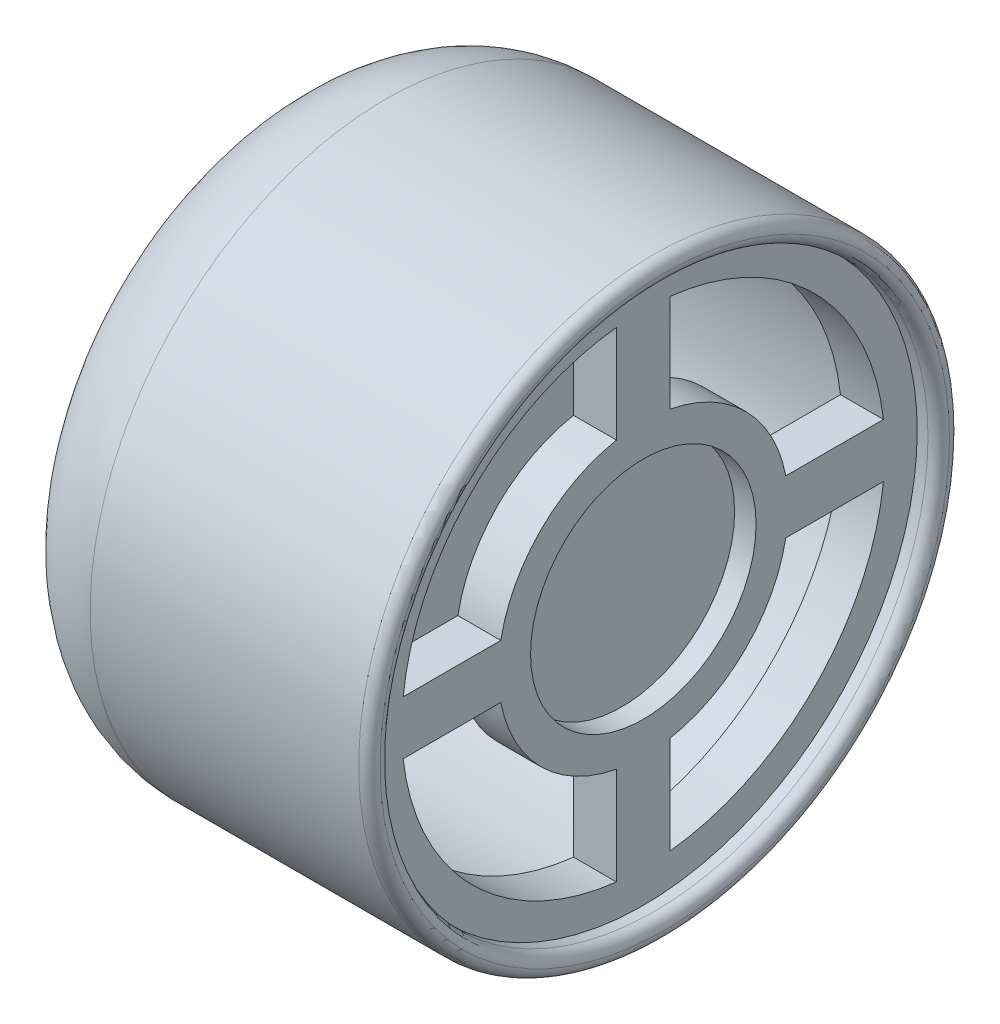
SolidWorks part; units mm, degrees
material "PLA"
ref_plane "Front Plane" through (0, 0, 0) normal (1, 0, 0) x (0, 1, 0)
ref_plane "Top Plane" through (0, 0, 0) normal (0, 0, 1) x (0, 1, 0)
ref_plane "Right Plane" through (0, 0, 0) normal (0, 1, 0) x (-1, 0, 0)
sketch "Sketch1" plane through (0, 0, 0) normal (1, 0, 0) x (0, 1, 0)
  line L0 (0, 6.5) -> (-20.5, 6.5)
  line L1 (0, 6.5) -> (0, -6.5)
  line L2 (0, -6.5) -> (-20.5, -6.5)
  line L3 (-20.5, 6.5) -> (-20.5, -6.5)
  line L4 (0, 0) -> (-24.2656, 0) construction
  line L5 (0, 6.5) -> (0, -6.5)
  line L6 (0, 19.7112) -> (0, -27.6906) construction
  line L7 (-16.5, 6.5) -> (7.5, 6.5)
  line L8 (-16.5, 6.5) -> (-16.5, -6.5)
  line L9 (-16.5, -6.5) -> (7.5, -6.5)
  line L10 (7.5, 6.5) -> (7.5, -6.5)
  circle A0 centre (0, 0) radius 10.25
  circle A1 centre (0, 0) radius 21.5058
  circle A3 centre (0, 0) radius 25.5058
  circle A4 centre (0, 0) radius 27.5058
  dimension "D1" = 20.5
  dimension "D2" = 20.5
  dimension "D3" = 13
  dimension "D4" = 24
  dimension "D5" = 7.5
  dimension "D6" = 4
  dimension "D7" = 2
extrude "Boss-Extrude1" add sketch "Sketch1" along normal blind 30 contours A4 A3 region at (0, -26.7278, 0)
sketch "Sketch2" plane through (30, 0, 0) normal (1, 0, 0) x (0, 1, 0)
  circle A0 centre (0, 0) radius 10.5
  circle A1 centre (0, 0) radius 27.5058
  circle A2 centre (0, 0) radius 27.5058
  circle M3 centre (0, 0) radius 25.5058
  circle M4 centre (0, 0) radius 27.5058
  dimension "D2" = 21
  dimension "D1" = 0
extrude "Boss-Extrude4" add sketch "Sketch2" along normal blind 6 contours M4 M3 region at (30, -26.7278, 0)
extrude "Boss-Extrude5" add sketch "Sketch2<4>" along normal blind 4 contours A0 M3 region at (30, -24.7844, 0)
sketch "Sketch2<4>" plane through (30, 0, 0) normal (1, 0, 0) x (0, 1, 0) same geometry as "Sketch2"
extrude "Boss-Extrude6" add sketch "Sketch2<5>" along normal blind 2 contours A0 region at (30, 0, 0)
sketch "Sketch2<5>" plane through (30, 0, 0) normal (1, 0, 0) x (0, 1, 0) same geometry as "Sketch2"
sketch "Sketch3" plane through (0, 0, 0) normal (-1, 0, 0) x (0, -1, 0)
  line L0 (0, 6.5) -> (-20.5, 6.5)
  line L1 (0, 6.5) -> (0, -6.5)
  line L2 (0, -6.5) -> (-20.5, -6.5)
  line L3 (-20.5, 6.5) -> (-20.5, -6.5)
  line L4 (0, 0) -> (27.3238, 0) construction
  line L5 (0, 6.5) -> (0, -6.5)
  line L6 (0, 25.2285) -> (0, -22.1733) construction
  line L7 (-16.5, 6.5) -> (7.5, 6.5)
  line L8 (-16.5, 6.5) -> (-16.5, -6.5)
  line L9 (-16.5, -6.5) -> (7.5, -6.5)
  line L10 (7.5, 6.5) -> (7.5, -6.5)
  circle A0 centre (0, 0) radius 12.5
  circle A1 centre (0, 0) radius 25.5058 construction
  circle A2 centre (0, 0) radius 27.5058 construction
  circle A3 centre (0, 0) radius 25.5058
  circle A4 centre (0, 0) radius 27.5058
  circle A5 centre (0, 0) radius 4
  circle A6 centre (0, 0) radius 21.5058
  circle A7 centre (51.6169, 6.4587) radius 23.5058
  circle M1 centre (0, 0) radius 25.5058
  circle M2 centre (0, 0) radius 27.5058
  dimension "D1" = 25
  dimension "D2" = 8
  dimension "D3" = 20.5
  dimension "D4" = 13
  dimension "D5" = 24
  dimension "D6" = 7.5
extrude "Boss-Extrude8" add sketch "Sketch3" against normal blind 6 contours L2 A6 L0 L7 A0 L9 | L3 A6 | A6 M1 | L2 A0 L0 L7 L10 L9 | M2 M1 | L8 L0 L3 L2 region at (0, 18.5, 0) region at (0, 18.5, 7.1012) region at (0, 20.9031, 0) region at (0, -3.2833, 11.7074) region at (0, 24.7844, 0) region at (0, 26.7278, 0)
sketch "Sketch8" plane through (34, 0, 0) normal (1, 0, 0) x (0, 1, 0)
  line L0 (-2.5, 22.3607) -> (-2.5, -22.3607)
  line L1 (2.5, 22.3607) -> (2.5, -22.3607)
  line L2 (-22.3607, 2.5) -> (22.3607, 2.5)
  line L3 (-22.3607, -2.5) -> (22.3607, -2.5)
  circle A0 centre (0, 0) radius 13.5
  circle A1 centre (0, 0) radius 22.5
  circle A2 centre (0, 0) radius 10.5 construction
  dimension "D1" = 3
  dimension "D2" = 9
  dimension "D3" = 5
extrude "Cut-Extrude3" cut sketch "Sketch8" against normal up to next contours L3 A1 L0 A0 | L0 A1 L2 A0 | L2 A1 L1 A0 | L1 A1 L3 A0 region at (34, -12.1516, 12.1516) region at (34, 12.1516, 12.1516) region at (34, -12.1516, -12.1516) region at (34, 12.1516, -12.1516)
sketch "Sketch9" plane through (0, 0, 0) normal (-1, 0, 0) x (0, -1, 0)
  line L5 (-10.5, -10.5) -> (10.5, -10.5)
  line L6 (-10.5, -10.5) -> (-10.5, 10.5)
  line L7 (-10.5, 10.5) -> (10.5, 10.5)
  line L8 (10.5, -10.5) -> (10.5, 10.5)
  line L9 (0, 10.5) -> (0, -10.5) construction
  line L10 (-10.5, 0) -> (10.5, 0) construction
  circle A4 centre (-10.5, 10.5) radius 1
  circle A5 centre (10.5, 10.5) radius 1
  circle A6 centre (10.5, -10.5) radius 1
  circle A7 centre (-10.5, -10.5) radius 1
  point P0 (0, 0)
  dimension "D2" = 2
  dimension "D1" = 21
extrude "Cut-Extrude4" cut sketch "Sketch9" against normal up to next and the other way through all contours L7 A4 L6 | L6 A4 L7 | L6 A7 L5 | L5 A7 L6 | L5 A6 L8 | L8 A6 L5 | L8 A5 L7 | L7 A5 L8 region at (0, 10.0756, -10.0756) region at (0, 10.6415, -10.6415) region at (0, -10.0756, -10.0756) region at (0, -10.6415, -10.6415) region at (0, 10.6415, 10.6415) region at (0, 10.0756, 10.0756) region at (0, -10.0756, 10.0756) region at (0, -10.6415, 10.6415)
fillet "Fillet9" radius 10 1 edges at (0, 0, -27.5058)
fillet "Fillet10" radius 1 2 edges at (36, 0, -25.5058) (36, 0, -27.5058)
